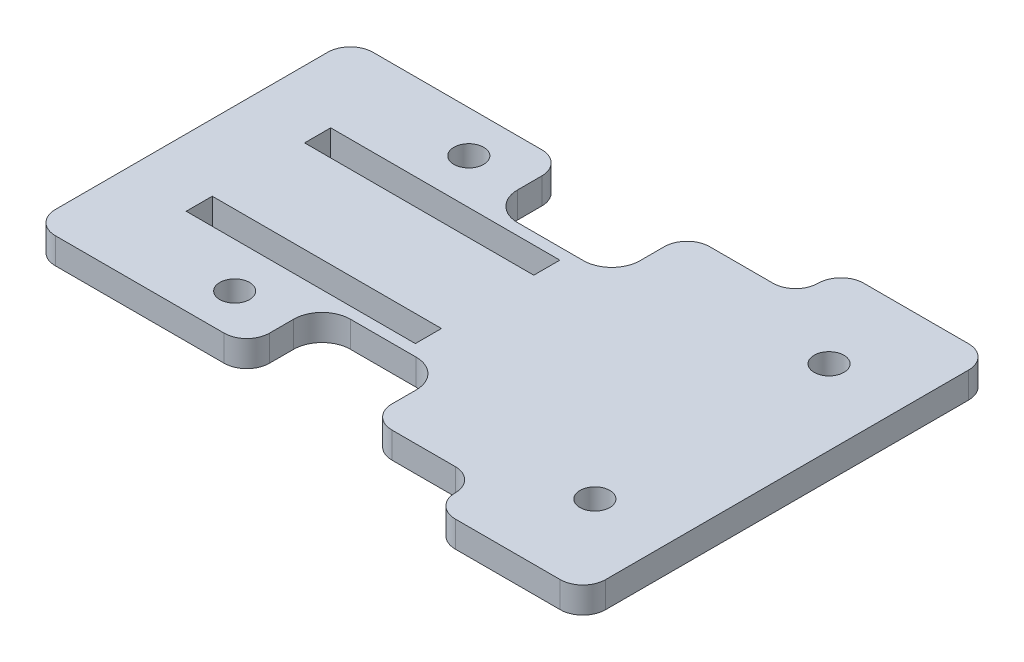
SolidWorks part; units mm, degrees
other "下垫片"
ref_plane "前视基准面" through (0, 0, 0) normal (0, 0, 1) x (1, 0, 0)
ref_plane "上视基准面" through (0, 0, 0) normal (0, 1, 0) x (1, 0, 0)
ref_plane "右视基准面" through (0, 0, 0) normal (1, 0, 0) x (0, 0, -1)
other "Configuration Table"
sketch "草图1" plane through (0, 0, 0) normal (0, 1, 0) x (1, 0, 0)
  line L0 (-89.3251, 0) -> (102.0425, 0) construction
  line L1 (0, 56.7239) -> (0, -62.578) construction
  line L2 (-48.2, -8.1375) -> (-7.8, -8.1375)
  line L3 (-48.2, 12.7375) -> (-7.8, 12.7375)
  line L4 (-48.2, 12.7375) -> (-48.2, 8.1375)
  line L5 (-48.2, 8.1375) -> (-7.8, 8.1375)
  line L6 (-7.8, 12.7375) -> (-7.8, 8.1375)
  line L7 (-48.2, 12.7375) -> (-7.8, 8.1375) construction
  line L8 (-48.2, 8.1375) -> (-7.8, 12.7375) construction
  line L9 (-7.8, -12.7375) -> (-7.8, -8.1375)
  line L10 (-48.2, -12.7375) -> (-7.8, -12.7375)
  line L11 (-48.2, -12.7375) -> (-48.2, -8.1375)
  line L14 (-22.25, -26.5375) -> (-22.25, -14.7375)
  line L15 (-22.25, -14.7375) -> (-0.65, -14.7375)
  line L16 (-0.65, -26.5375) -> (-0.65, -14.7375)
  line L17 (-22.25, -26.5375) -> (-0.65, -14.7375) construction
  line L18 (-22.25, -14.7375) -> (-0.65, -26.5375) construction
  line L19 (-22.25, 14.7375) -> (-0.65, 14.7375)
  line L20 (-0.65, 26.5375) -> (-0.65, 14.7375)
  line L22 (-22.25, 26.5375) -> (-22.25, 14.7375)
  line L23 (-22.25, 30.0095) -> (-0.65, 30.0095)
  line L25 (-22.25, -26.5375) -> (-22.25, -30.0095)
  line L26 (-22.25, -30.0095) -> (-0.65, -30.0095)
  line L27 (-0.65, -26.5375) -> (-0.65, -30.0095)
  line L28 (-0.65, 26.5375) -> (-0.65, 30.0095)
  line L30 (-22.25, 26.5375) -> (-22.25, 30.0095)
  circle A0 centre (-31.75, 20.6375) radius 2.625
  circle A4 centre (31.75, 20.6375) radius 2.625
  circle A5 centre (31.75, -20.6375) radius 2.625
  circle A6 centre (-31.75, -20.6375) radius 2.625
  point P13 (-28, 10.4375)
  point P22 (-11.45, -20.6375)
  point P35 (-28, 10.4375)
  dimension "D5" = 5.25
  dimension "D11" = 5.25
  dimension "D1" = 40.4
  dimension "D2" = 31.75
  dimension "D3" = 4.6
  dimension "D4" = 20.6375
  dimension "D6" = 9.5
  dimension "D7" = 21.6
  dimension "D8" = 11.8
  dimension "D9" = 0
  dimension "D10" = 32.4
  dimension "D12" = 4.6
  dimension "D13" = 40.4
  dimension "D14" = 28
  dimension "D15" = 10.4375
  dimension "D16" = 2
sketch "草图3" plane through (0, 0, 0) normal (0, 1, 0) x (1, 0, 0)
  line L0 (-40, 28) -> (-60, 28)
  line L1 (-40, -28) -> (18.5, -28)
  line L3 (-40, 28) -> (18.5, 28)
  line L5 (-40, -28) -> (40, 28) construction
  line L6 (-40, 28) -> (40, -28) construction
  line L7 (-60, 28) -> (-60, -28)
  line L8 (-60, -28) -> (-40, -28)
  line L10 (45, 28) -> (45, -28)
  line L12 (45, -28) -> (45, -36)
  line L13 (45, -36) -> (18.5, -36)
  line L14 (18.5, -36) -> (18.5, -28)
  line L15 (-45.7746, 0) -> (58.2399, 0) construction
  line L16 (45, 28) -> (45, 36)
  line L17 (45, 36) -> (18.5, 36)
  line L18 (18.5, 36) -> (18.5, 28)
  point P0 (0, 0)
  dimension "D1" = 56
  dimension "D2" = 80
  dimension "D3" = 20
  dimension "D4" = 5
  dimension "D5" = 26.5
  dimension "D6" = 8
extrude "凸台-拉伸1" add sketch "草图3" along normal blind 4.6
extrude "切除-拉伸1" cut sketch "草图1" along normal up to surface (4.6 mm away) up to face at (5.5, 4.6, 0)
fillet "圆角1" radius 5 4 edges at (-0.65, 2.3, 14.7375) (-22.25, 2.3, 14.7375) (-0.65, 2.3, -14.7375) (-22.25, 2.3, -14.7375)
fillet "圆角2" radius 4 12 edges at (-0.65, 2.3, 28) (-22.25, 2.3, 28) (-0.65, 2.3, -28) (-22.25, 2.3, -28) (-60, 2.3, 28) (-60, 2.3, -28) (18.5, 2.3, -28) (18.5, 2.3, -36) (45, 2.3, -36) (45, 2.3, 36) (18.5, 2.3, 36) (18.5, 2.3, 28)
